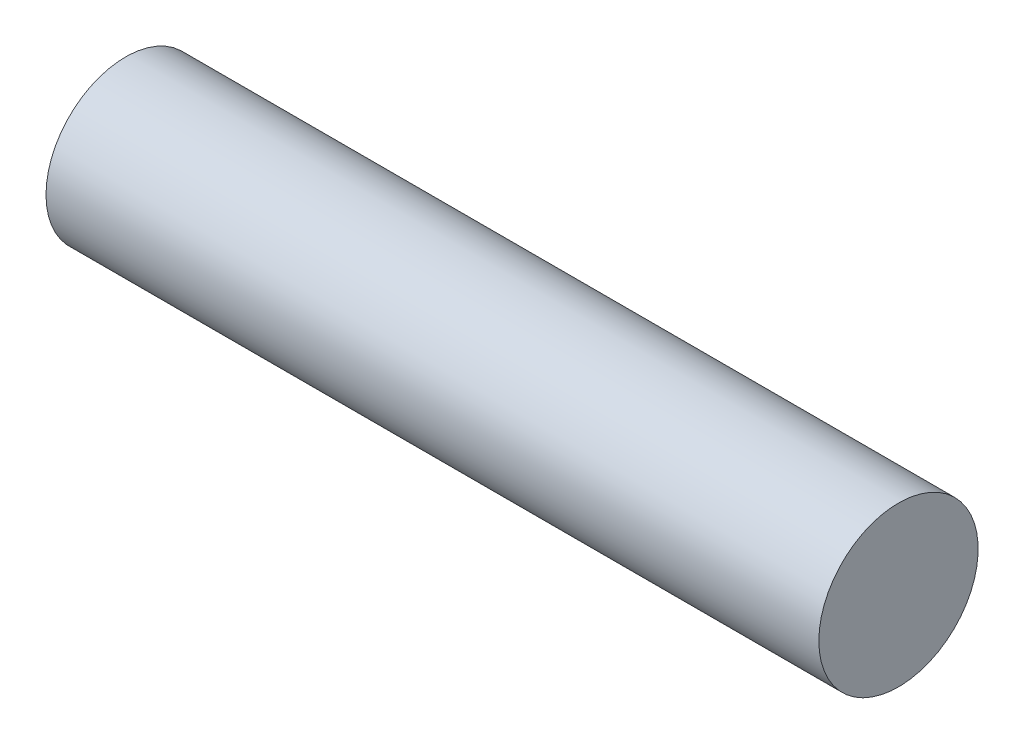
SolidWorks part; units mm, degrees
ref_plane "Front Plane" through (0, 0, 0) normal (0, 0, 1) x (1, 0, 0)
ref_plane "Top Plane" through (0, 0, 0) normal (0, 1, 0) x (1, 0, 0)
ref_plane "Right Plane" through (0, 0, 0) normal (1, 0, 0) x (0, 0, -1)
sketch "Leg_Cartridge Sketch" plane through (0, 0, 0) normal (0, 0, 1) x (1, 0, 0)
  line L0 (-3000, 0) -> (3000, 0) construction
  line L1 (1110, 0) -> (1240, 0)
  line L2 (1240, 0) -> (1240, 13.4)
  line L3 (1240, 13.4) -> (1110, 13.4)
  line L4 (1110, 13.4) -> (1110, 0)
revolve "Leg_Cartridge" add sketch "Leg_Cartridge Sketch" angle 360 about L0
ref_axis "Engine Axis" through (1246.5, 0, 0) along (-1, 0, 0)
